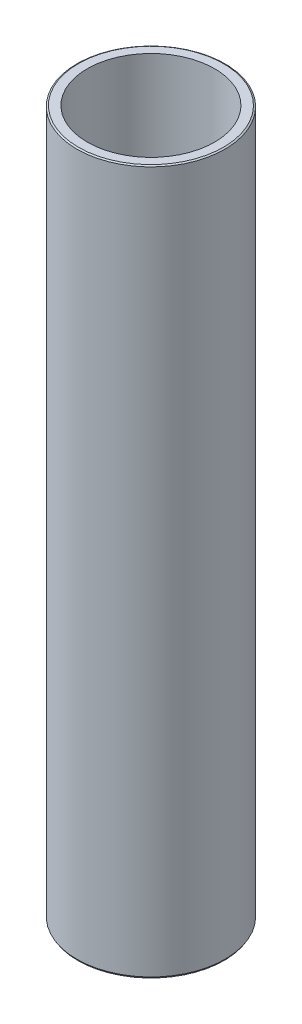
SolidWorks part; units mm, degrees
ref_plane "Front Plane" through (0, 0, 0) normal (0, 0, 1) x (1, 0, 0)
ref_plane "Top Plane" through (0, 0, 0) normal (0, 1, 0) x (1, 0, 0)
ref_plane "Right Plane" through (0, 0, 0) normal (1, 0, 0) x (0, 0, -1)
sketch "Sketch1" plane through (0, 0, 0) normal (0, 1, 0) x (1, 0, 0)
  circle A0 centre (0, 0) radius 60
  dimension "SHAFT_OD" = 120
extrude "Boss-Extrude1" add sketch "Sketch1" along normal blind 570.494
sketch "Sketch2" plane through (0, 0, 0) normal (0, 1, 0) x (1, 0, 0)
  circle A0 centre (0, 0) radius 51.5938
  dimension "BORE_D" = 103.1876
extrude "Cut-Extrude1" cut sketch "Sketch2" along normal through all
chamfer "Chamfer1" distance 0.7179 angle 60 2 edges at (0, 570.494, 60) (0, 0, 60) first distance on face at (0, 570.494, 60) first distance on face at (0, 0, 51.5938)
